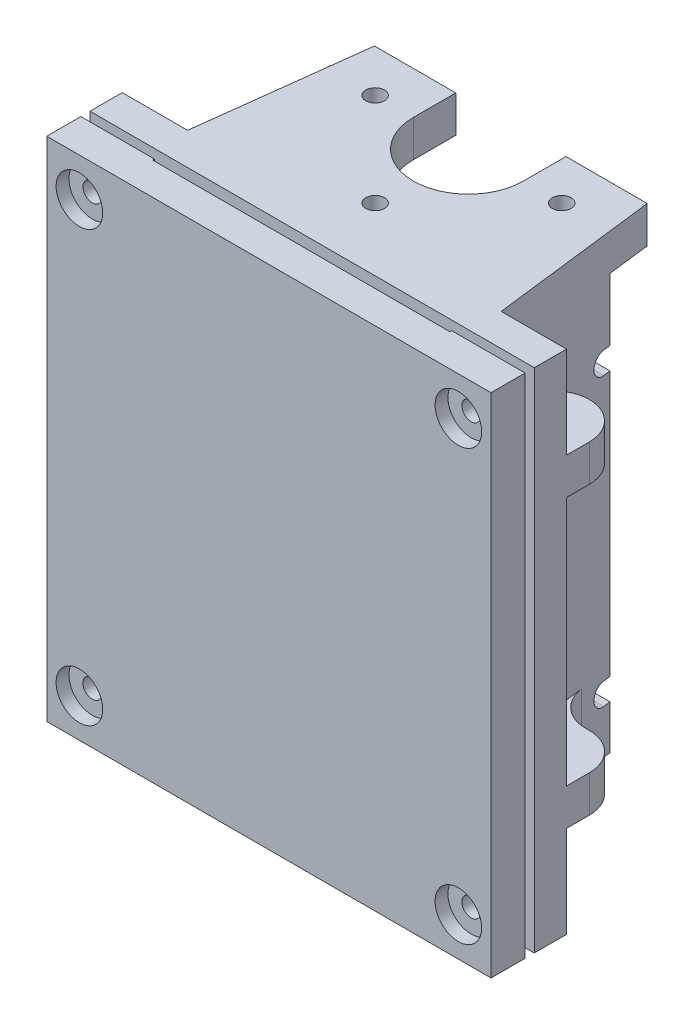
SolidWorks part; units mm, degrees
ref_plane "Front Plane" through (0, 0, 0) normal (0, 0, 1) x (1, 0, 0)
ref_plane "Top Plane" through (0, 0, 0) normal (0, 1, 0) x (1, 0, 0)
ref_plane "Right Plane" through (0, 0, 0) normal (1, 0, 0) x (0, 0, -1)
sketch "Sketch1" plane through (0, 0, 0) normal (0, 1, 0) x (1, 0, 0)
  line L0 (-32.5572, 0) -> (-38.5572, 0)
  line L5 (-38.5572, 0) -> (-42.7047, -33.7788)
  line L7 (42.7047, -33.7788) -> (38.5572, 0)
  line L8 (38.5572, 0) -> (32.5572, 0)
  line L9 (-42.7047, -33.7788) -> (-60.4847, -33.7788)
  line L10 (-60.4847, -33.7788) -> (-60.4847, -42.5572)
  line L11 (-60.4847, -42.5572) -> (60.4847, -42.5572)
  line L12 (60.4847, -42.5572) -> (60.4847, -33.7788)
  line L13 (60.4847, -33.7788) -> (42.7047, -33.7788)
  line L14 (0, 0) -> (0, -32.5572) construction
  line L15 (38.5572, 0) -> (38.5572, -26.0046) construction
  line L16 (51.5947, -33.7788) -> (51.5947, -54.3356) construction
  line L17 (-60.4847, -45.5572) -> (60.4847, -45.5572)
  line L18 (-60.4847, -45.5572) -> (-60.4847, -54.3356)
  line L19 (-60.4847, -54.3356) -> (60.4847, -54.3356)
  line L20 (60.4847, -45.5572) -> (60.4847, -54.3356)
  line L21 (49.042, -33.7788) -> (49.042, -54.3356) construction
  line L23 (54.1474, -33.7788) -> (54.1474, -54.3356) construction
  line L26 (46.8322, -36.9538) -> (56.3572, -36.9538) construction
  line L27 (46.8322, -36.9538) -> (46.8322, -33.7788) construction
  line L28 (46.8322, -33.7788) -> (56.3572, -33.7788) construction
  line L29 (56.3572, -36.9538) -> (56.3572, -33.7788) construction
  line L30 (46.8322, -36.9538) -> (56.3572, -33.7788) construction
  line L31 (46.8322, -33.7788) -> (56.3572, -36.9538) construction
  line L32 (49.9992, -31.7788) -> (74.4903, -31.7788) construction
  line L33 (45.2447, -55.9088) -> (57.9447, -55.9088) construction
  line L34 (45.2447, -55.9088) -> (45.2447, -50.8288) construction
  line L35 (45.2447, -50.8288) -> (57.9447, -50.8288) construction
  line L36 (57.9447, -55.9088) -> (57.9447, -50.8288) construction
  line L37 (45.2447, -55.9088) -> (57.9447, -50.8288) construction
  line L38 (45.2447, -50.8288) -> (57.9447, -55.9088) construction
  circle A0 centre (0, 0) radius 32.5572 construction
  arc A1 (-32.5572, 0) -> (32.5572, 0) centre (0, 0) ccw
  point P6 (0, 0)
  point P8 (0, 0)
  point P27 (51.5947, -35.3663)
  point P32 (51.5947, -53.3688)
  point P39 (0, 0)
  point P42 (59.3572, -45.7404)
  point P43 (61.588, -50.3356)
  point P44 (42.7047, -33.7788)
  point P47 (-42.7047, -33.7788)
  dimension "D1" = 65.1144
  dimension "D2" = 10
  dimension "D3" = 6
  dimension "D4" = 7
  dimension "D6" = 3
  dimension "D5" = 5.1054
  dimension "D7" = 9.525
  dimension "D8" = 3.175
  dimension "D9" = 2
  dimension "D11" = 12.7
  dimension "D12" = 5.08
  dimension "D13" = 2.54
  dimension "D10" = 19.05
  dimension "D14" = 5.6034
extrude "Boss-Extrude1" add sketch "Sketch1" along normal mid plane 113.03 contours A1 L8 L7 L13 L12 L11 L10 L9 L5 L0
sketch "Sketch4" plane through (0, -56.515, 0) normal (0, -1, 0) x (1, 0, 0)
  line L0 (-60.4847, 33.7788) -> (-60.4847, 42.5572) construction
  line L1 (60.4847, 42.5572) -> (-60.4847, 42.5572)
  line L2 (60.4847, 42.5572) -> (60.4847, 33.7788)
  line L4 (-60.4847, 42.5572) -> (-60.4847, 33.7788)
  line L5 (60.4847, 33.7788) -> (42.7047, 33.7788)
  line L6 (42.7047, 33.7788) -> (38.5572, 0) construction
  line L7 (42.7047, 33.7788) -> (40.399, 15)
  line L8 (40.399, 15) -> (-40.399, 15) construction
  line L9 (-38.5572, 0) -> (-42.7047, 33.7788) construction
  line L10 (-40.399, 15) -> (-42.7047, 33.7788)
  line L11 (-42.7047, 33.7788) -> (-60.4847, 33.7788)
  line L12 (40.399, 15) -> (13.2288, 15)
  line L13 (-40.399, 15) -> (-13.2288, 15)
  line L14 (-42.7047, 33.7788) -> (-60.4847, 33.7788) construction
  circle A0 centre (0, 0) radius 20 construction
  arc A1 (13.2288, 15) -> (-13.2288, 15) centre (0, 0) ccw
  arc A2 (32.5572, 0) -> (-32.5572, 0) centre (0, 0) ccw construction
  dimension "D2" = 40
  dimension "D3" = 15
extrude "Boss-Extrude2" add sketch "Sketch4" along normal blind 15
sketch "Sketch5" plane through (0, 56.515, 0) normal (0, 1, 0) x (1, 0, 0)
  line L0 (-42.7047, -33.7788) -> (-37.1387, 11.5527)
  line L1 (-60.4847, -42.5572) -> (60.4847, -42.5572)
  line L2 (-60.4847, -42.5572) -> (-60.4847, -33.7788)
  line L3 (-60.4847, -33.7788) -> (60.4847, -33.7788) construction
  line L4 (60.4847, -42.5572) -> (60.4847, -33.7788)
  line L5 (-37.1387, 11.5527) -> (-15, 11.5527)
  line L6 (37.1387, 11.5527) -> (42.7047, -33.7788)
  line L7 (-42.7047, -33.7788) -> (-60.4847, -33.7788) construction
  line L8 (42.7047, -33.7788) -> (38.5572, 0) construction
  line L9 (-38.5572, 0) -> (-42.7047, -33.7788) construction
  line L10 (-60.4847, -33.7788) -> (-42.7047, -33.7788)
  line L11 (42.7047, -33.7788) -> (60.4847, -33.7788)
  line L12 (-15, 11.5527) -> (-15, 0)
  line L13 (15, 11.5527) -> (15, 0)
  line L14 (15, 11.5527) -> (37.1387, 11.5527)
  line L15 (60.4847, -42.5572) -> (60.4847, -33.7788) construction
  circle A0 centre (0, 0) radius 25.4 construction
  circle A1 centre (0, -25.4) radius 2.5527
  circle A2 centre (25.4, 0) radius 2.5527
  circle A3 centre (-25.4, 0) radius 2.5527
  arc A4 (-15, 0) -> (15, 0) centre (0, 0) ccw
  point P8 (0, 0)
  point P24 (-17.5766, 9.4973)
  point P29 (0, 0)
  dimension "D1" = 50.8
  dimension "D2" = 5.1054
  dimension "D3" = 15
  dimension "D4" = 9
extrude "Boss-Extrude3" add sketch "Sketch5" along normal blind 10
sketch "Sketch7" plane through (0, 0, 33.7788) normal (0, 0, -1) x (-1, 0, 0)
  line L0 (51.5947, 66.515) -> (51.5947, -71.515) construction
  line L1 (42.7047, 66.515) -> (60.4847, 66.515) construction
  line L2 (60.4847, -71.515) -> (42.7047, -71.515) construction
  line L3 (60.4847, -2.5) -> (-60.4847, -2.5) construction
  line L4 (60.4847, 66.515) -> (60.4847, -71.515) construction
  line L5 (-60.4847, 66.515) -> (-60.4847, -71.515) construction
  line L6 (46.8322, -58.2661) -> (51.5947, -55.5165)
  line L7 (51.5947, 50.5165) -> (56.3572, 53.2661)
  line L8 (56.3572, 53.2661) -> (56.3572, 58.7654)
  line L9 (56.3572, 58.7654) -> (51.5947, 61.515)
  line L10 (51.5947, 61.515) -> (46.8322, 58.7654)
  line L11 (46.8322, 58.7654) -> (46.8322, 53.2661)
  line L12 (46.8322, 53.2661) -> (51.5947, 50.5165)
  line L13 (46.8322, -63.7654) -> (46.8322, -58.2661)
  line L14 (51.5947, -66.515) -> (46.8322, -63.7654)
  line L15 (56.3572, -63.7654) -> (51.5947, -66.515)
  line L16 (56.3572, -58.2661) -> (56.3572, -63.7654)
  line L17 (51.5947, -55.5165) -> (56.3572, -58.2661)
  line L18 (0, 0) -> (0, -85.6539) construction
  line L19 (-51.5947, -55.5165) -> (-56.3572, -58.2661)
  line L20 (-56.3572, -58.2661) -> (-56.3572, -63.7654)
  line L21 (-56.3572, -63.7654) -> (-51.5947, -66.515)
  line L22 (-51.5947, -66.515) -> (-46.8322, -63.7654)
  line L23 (-46.8322, -63.7654) -> (-46.8322, -58.2661)
  line L24 (-46.8322, 53.2661) -> (-51.5947, 50.5165)
  line L25 (-46.8322, 58.7654) -> (-46.8322, 53.2661)
  line L26 (-51.5947, 61.515) -> (-46.8322, 58.7654)
  line L27 (-56.3572, 58.7654) -> (-51.5947, 61.515)
  line L28 (-56.3572, 53.2661) -> (-56.3572, 58.7654)
  line L29 (-51.5947, 50.5165) -> (-56.3572, 53.2661)
  line L30 (-46.8322, -58.2661) -> (-51.5947, -55.5165)
  circle A0 centre (51.5947, 56.0157) radius 4.7625 construction
  circle A1 centre (51.5947, -61.0157) radius 4.7625 construction
  circle A2 centre (-51.5947, -61.0157) radius 4.7625 construction
  circle A3 centre (-51.5947, 56.0157) radius 4.7625 construction
  dimension "D1" = 9.525
  dimension "D2" = 5
ref_plane "Plane1" through (0, 0, 36.9538) normal (0, 0, -1) x (-1, 0, 0)
extrude "Cut-Extrude1" cut sketch "Sketch7" against normal up to surface (3.175 mm away) up to plane "Plane1"
sketch "Sketch9" plane through (0, 0, 33.7788) normal (0, 0, -1) x (-1, 0, 0)
  circle A0 centre (51.5947, 56.0157) radius 2.5527
  circle A1 centre (51.5947, -61.0157) radius 2.5527
  circle A2 centre (-51.5947, -61.0157) radius 2.5527
  circle A3 centre (-51.5947, 56.0157) radius 2.5527
  dimension "D1" = 5.1054
extrude "Cut-Extrude2" cut sketch "Sketch9" against normal up to next
extrude "Boss-Extrude4" add sketch "Sketch1<3>" along normal up to surface and the other way up to surface separate body contours L19 L20 L17 L18 up to face at (25.4, 66.515, 2.5527) other way up to face at (0, -71.515, 28.523)
sketch "Sketch1<3>" plane through (0, 0, 0) normal (0, 1, 0) x (1, 0, 0) same geometry as "Sketch1"
sketch "Sketch10" plane through (0, 0, 54.3356) normal (0, 0, 1) x (1, 0, 0)
  circle A0 centre (-51.5947, 56.0157) radius 6.35
  circle A1 centre (51.5947, 56.0157) radius 6.35
  circle A2 centre (51.5947, -61.0157) radius 6.35
  circle A3 centre (-51.5947, -61.0157) radius 6.35
  dimension "D1" = 12.7
extrude "Cut-Extrude3" cut sketch "Sketch10" against normal up to vertex (3.5067 mm away) up to point (57.9447, 0, 50.8288)
sketch "Sketch11" plane through (0, 66.515, 0) normal (0, 1, 0) x (1, 0, 0)
  line L0 (-60.4847, -45.5572) -> (-60.4847, -45.0572)
  line L1 (-60.4847, -45.0572) -> (-40.4847, -45.0572)
  line L2 (-40.4847, -45.0572) -> (-40.4847, -45.5572)
  line L3 (-60.4847, -45.5572) -> (60.4847, -45.5572) construction
  line L4 (-40.4847, -45.5572) -> (-60.4847, -45.5572)
  line L5 (0, -45.5572) -> (0, -54.3356) construction
  line L6 (-60.4847, -54.3356) -> (60.4847, -54.3356) construction
  line L7 (40.4847, -45.5572) -> (60.4847, -45.5572)
  line L8 (40.4847, -45.0572) -> (40.4847, -45.5572)
  line L9 (60.4847, -45.0572) -> (40.4847, -45.0572)
  line L10 (60.4847, -45.5572) -> (60.4847, -45.0572)
  dimension "D1" = 0.5
  dimension "D2" = 20
extrude "Boss-Extrude5" add sketch "Sketch11" against normal up to surface (138.03 mm away) up to face at (0, -71.515, 49.9464)
extrude "Cut-Extrude4" cut sketch "Sketch9<2>" against normal through all both and the other way through all contours A1 | A2 | A3 | A0
sketch "Sketch9<2>" plane through (0, 0, 33.7788) normal (0, 0, -1) x (-1, 0, 0) same geometry as "Sketch9"
ref_plane "Plane2" through (0, -36.515, 0) normal (0, -1, 0) x (-1, 0, 0)
sketch "Sketch13" plane through (0, -36.515, 0) normal (0, -1, 0) x (-1, 0, 0)
  line L0 (0, 0) -> (0, -54.3356) construction
  line L1 (60.4847, -54.3356) -> (-60.4847, -54.3356) construction
  line L2 (-60.4847, -27.5572) -> (-60.4847, -42.5572)
  line L3 (-60.4847, -42.5572) -> (-40.4847, -42.5572)
  line L4 (-60.4847, -42.5572) -> (60.4847, -42.5572) construction
  line L5 (-40.4847, -42.5572) -> (-40.4847, -27.5572)
  circle A0 centre (-50.4847, -27.5572) radius 10 construction
  circle A1 centre (-50.4847, -27.5572) radius 2
  arc A2 (-60.4847, -27.5572) -> (-40.4847, -27.5572) centre (-50.4847, -27.5572) cw
  point P0 (-39.1722, -28.0871)
  point P18 (0, 0)
  dimension "D1" = 4
  dimension "D2" = 10
  dimension "D3" = 15
extrude "Boss-Extrude6" add sketch "Sketch13" along normal blind 10
fillet "Fillet2" radius 10 1 edges at (41.4218, -41.515, 23.3306)
sketch "Sketch15" plane through (0, 0, 0) normal (1, 0, 0) x (0, 0, -1)
  line L5 (-8.7972, -41.515) -> (0, -41.515) construction
  line L6 (-8.7972, -36.515) -> (-8.7972, -46.515) construction
  line L7 (0, 56.515) -> (0, -56.515) construction
  line L8 (-2, -41.515) -> (0, -41.515) construction
  line L9 (-2, -38.515) -> (0, -38.515)
  line L10 (-2, -44.515) -> (0, -44.515)
  arc A0 (-2, -38.515) -> (-2, -44.515) centre (-2, -41.515) ccw
  arc A1 (0, -44.515) -> (0, -38.515) centre (0, -41.515) ccw
  point P7 (-1, -41.515)
  dimension "D1" = 3
  dimension "D2" = 2
extrude "Cut-Extrude5" cut sketch "Sketch15" against normal through all both and the other way through all
mirror "Mirror1" about plane through (0, 0, 0) normal (1, 0, 0) of "Boss-Extrude6"
fillet "Fillet4" radius 10 1 edges at (-41.4218, -41.515, 23.3306)
ref_plane "Plane3" through (0, -2.5, 0) normal (0, -1, 0) x (-1, 0, 0)
mirror "Mirror2" about plane through (0, -2.5, 0) normal (0, -1, 0) of "Fillet4", "Cut-Extrude5", "Mirror1"
equation "\"D1@Sketch1\"=2.536in+0.7mm"
equation "\"D5@Sketch1\"=0.201in"
equation "\"D7@Sketch1\"=0.375in"
equation "\"D6@Sketch1\"=3mm"
equation "\"D10@Sketch1\"=0.75in"
equation "\"D1@Boss-Extrude1\"=4.45in"
equation "\"D1@Sketch5\"=2in"
equation "\"D2@Sketch5\"=0.201in"
equation "\"D1@Sketch7\"=0.375in"
equation "\"D1@Sketch9\"=0.201in"
equation "\"D1@Sketch10\"=12.7"
